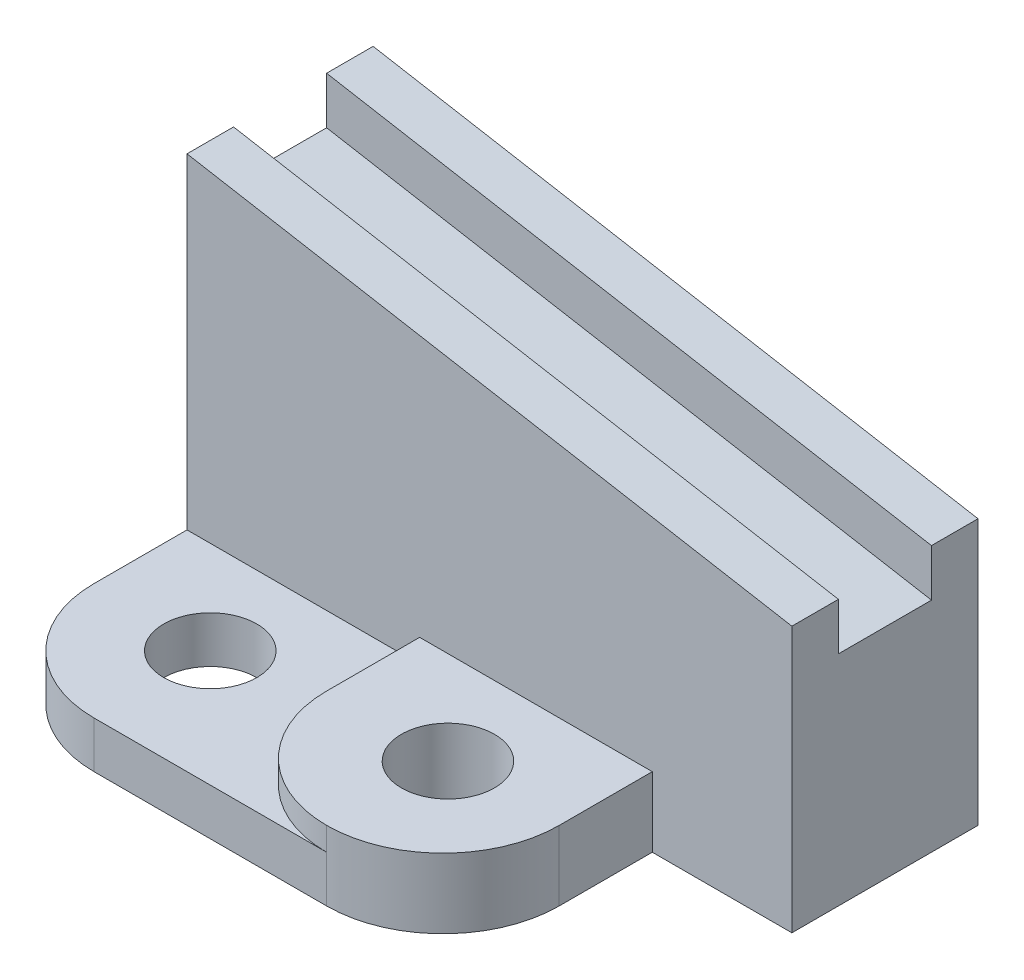
SolidWorks part; units mm, degrees
ref_plane "Plano frontal" through (0, 0, 0) normal (0, 0, 1) x (1, 0, 0)
ref_plane "Plano superior" through (0, 0, 0) normal (0, 1, 0) x (1, 0, 0)
ref_plane "Plano direito" through (0, 0, 0) normal (1, 0, 0) x (0, 0, -1)
sketch "Esboço1" plane through (0, 0, 0) normal (0, 0, 1) x (1, 0, 0)
  line L0 (-53.2953, 9.3008) -> (76.7047, 9.3008)
  line L1 (-53.2953, 9.3008) -> (-53.2953, 89.3008)
  line L2 (76.7047, 9.3008) -> (76.7047, 66.3783)
  line L3 (-53.2953, 89.3008) -> (76.7047, 66.3783)
  dimension "D1" = 100
  dimension "D2" = 80
  dimension "D3" = 130
extrude "Ressalto-extrusão1" add sketch "Esboço1" along normal blind 40
sketch "Esboço3" [suppressed] plane through (13.6643, 77.494, 0) normal (0.1736, 0.9848, 0) x (0.9848, -0.1736, 0)
  line L0 (64.0129, -40) -> (-67.9926, -40) construction
  line L1 (-71.0201, -30) -> (70.4962, -30)
  line L2 (-71.0201, -30) -> (-71.0201, -10)
  line L3 (-71.0201, -10) -> (70.4962, -10)
  line L4 (70.4962, -30) -> (70.4962, -10)
  line L5 (64.0129, 0) -> (-67.9926, 0) construction
  dimension "D1" = 10
  dimension "D2" = 10
extrude "Corte-extrusão2" [suppressed] cut sketch "Esboço3" against normal blind 10
sketch "Esboço4" plane through (13.6643, 77.494, 0) normal (0.1736, 0.9848, 0) x (0.9848, -0.1736, 0)
  line L0 (64.0129, 0) -> (-67.9926, 0) construction
  line L1 (-77.3839, -10) -> (94.2466, -10)
  line L2 (-77.3839, -10) -> (-77.3839, -30)
  line L3 (-77.3839, -30) -> (94.2466, -30)
  line L4 (94.2466, -10) -> (94.2466, -30)
  line L5 (64.0129, -40) -> (-67.9926, -40) construction
  dimension "D1" = 10
  dimension "D2" = 10
extrude "Corte-extrusão3" cut sketch "Esboço4" against normal blind 10
sketch "Esboço5" plane through (0, 0, 40) normal (0, 0, 1) x (1, 0, 0)
  line L1 (-53.2953, 9.3008) -> (46.7047, 9.3008)
  line L2 (-53.2953, 9.3008) -> (-53.2953, 24.3008)
  line L3 (-53.2953, 24.3008) -> (46.7047, 24.3008)
  line L4 (46.7047, 9.3008) -> (46.7047, 24.3008)
  dimension "D1" = 15
  dimension "D2" = 100
extrude "Ressalto-extrusão2" add sketch "Esboço5" along normal blind 45
fillet "Filete6" radius 25 1 edges at (-53.2953, 16.8008, 85) type face fillet first side face at (-53.2953, 61.52, 35.25) second side face at (-3.2953, 16.8008, 85)
fillet "Filete7" radius 25 1 edges at (46.7047, 16.8008, 85) type face fillet first side face at (9.2047, 16.8008, 85) second side face at (46.7047, 14.9258, 68.125)
sketch "Esboço7" plane through (0, 24.3008, 0) normal (0, 1, 0) x (1, 0, 0)
  line L0 (21.7047, -85) -> (-28.2953, -85) construction
  circle A0 centre (-28.2953, -60) radius 10
  circle A1 centre (22.7777, -60) radius 10
  dimension "D1" = 20
  dimension "D2" = 20
  dimension "D3" = 25
extrude "Corte-extrusão4" cut sketch "Esboço7" against normal through all
sketch "Esboço8" plane through (0, 24.3008, 0) normal (0, 1, 0) x (1, 0, 0)
  line L0 (21.7047, -85) -> (-28.2953, -85) construction
  line L1 (-53.2953, -40) -> (-3.2953, -40)
  line L2 (-53.2953, -40) -> (-53.2953, -85)
  line L3 (-53.2953, -85) -> (-3.2953, -85)
  line L4 (-3.2953, -40) -> (-3.2953, -85)
extrude "Corte-extrusão5" cut sketch "Esboço8" against normal blind 5
fillet "Filete8" radius 25 1 edges at (-3.2953, 21.8008, 85) type face fillet first side face at (-3.2953, 21.8008, 62.5) second side face at (-3.2953, 17.6342, 85)
